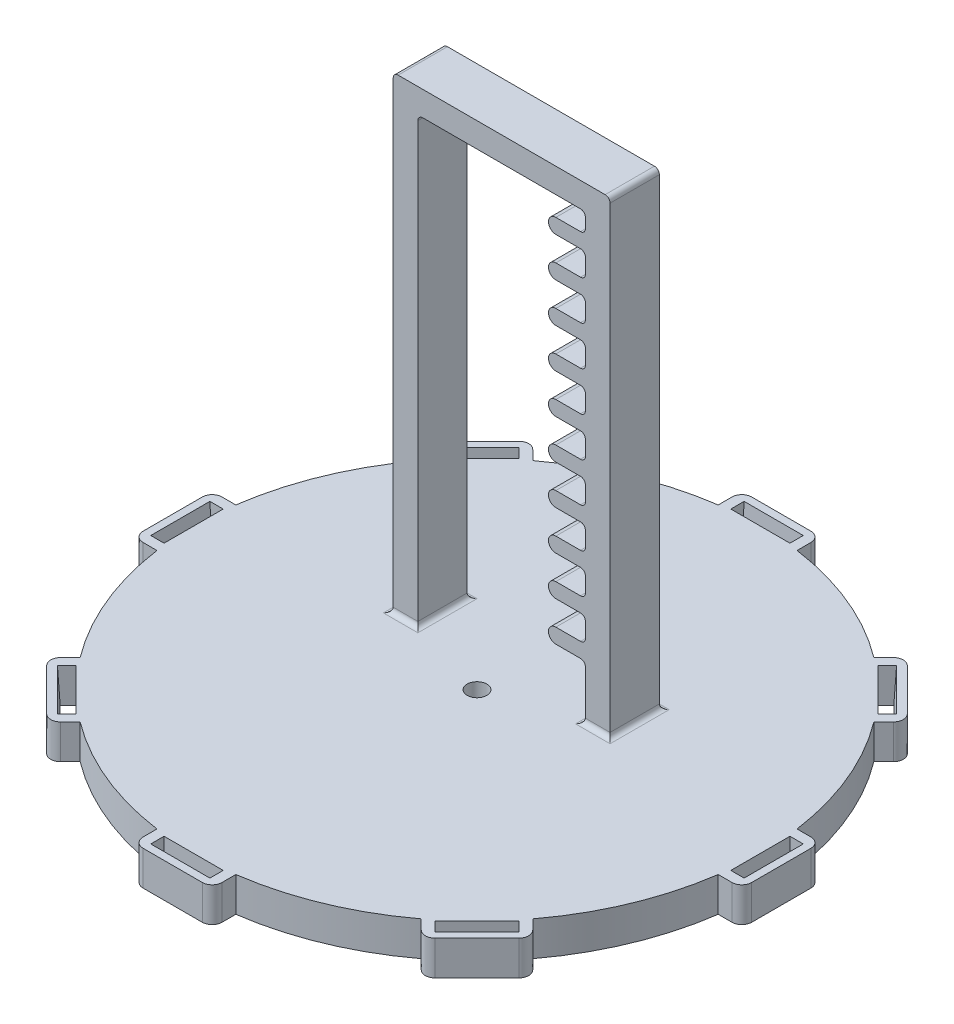
SolidWorks part; units mm, degrees
ref_plane "Front Plane" through (0, 0, 0) normal (0, 0, 1) x (1, 0, 0)
ref_plane "Top Plane" through (0, 0, 0) normal (0, 1, 0) x (1, 0, 0)
ref_plane "Right Plane" through (0, 0, 0) normal (1, 0, 0) x (0, 0, -1)
sketch "Sketch1" plane through (0, 0, 0) normal (0, 1, 0) x (1, 0, 0)
  line L0 (-8, 56.9408) -> (-8, 59.7408)
  line L1 (0, 57.5) -> (0, -57.5) construction
  line L2 (8, 56.9408) -> (8, 59.7408)
  line L3 (-6, 61.7408) -> (6, 61.7408)
  line L4 (39.4147, 47.8999) -> (47.8999, 39.4147)
  line L9 (34.6063, 45.9201) -> (36.5862, 47.8999)
  line L10 (45.9201, 34.6063) -> (47.8999, 36.5862)
  line L15 (61.7408, 6) -> (61.7408, -6)
  line L16 (56.9408, 8) -> (59.7408, 8)
  line L17 (56.9408, -8) -> (59.7408, -8)
  line L22 (47.8999, -39.4147) -> (39.4147, -47.8999)
  line L23 (45.9201, -34.6063) -> (47.8999, -36.5862)
  line L24 (34.6063, -45.9201) -> (36.5862, -47.8999)
  line L29 (6, -61.7408) -> (-6, -61.7408)
  line L30 (8, -56.9408) -> (8, -59.7408)
  line L31 (-8, -56.9408) -> (-8, -59.7408)
  line L36 (-39.4147, -47.8999) -> (-47.8999, -39.4147)
  line L37 (-34.6063, -45.9201) -> (-36.5862, -47.8999)
  line L38 (-45.9201, -34.6063) -> (-47.8999, -36.5862)
  line L43 (-61.7408, -6) -> (-61.7408, 6)
  line L44 (-56.9408, -8) -> (-59.7408, -8)
  line L45 (-56.9408, 8) -> (-59.7408, 8)
  line L50 (-47.8999, 39.4147) -> (-39.4147, 47.8999)
  line L51 (-45.9201, 34.6063) -> (-47.8999, 36.5862)
  line L52 (-34.6063, 45.9201) -> (-36.5862, 47.8999)
  arc A0 (-8, 56.9408) -> (-34.6063, 45.9201) centre (0, 0) ccw
  arc A1 (6, 61.7408) -> (8, 59.7408) centre (6, 59.7408) cw
  arc A2 (-6, 61.7408) -> (-8, 59.7408) centre (-6, 59.7408) ccw
  arc A3 (39.4147, 47.8999) -> (36.5862, 47.8999) centre (38.0005, 46.4857) ccw
  arc A4 (47.8999, 39.4147) -> (47.8999, 36.5862) centre (46.4857, 38.0005) cw
  arc A5 (61.7408, 6) -> (59.7408, 8) centre (59.7408, 6) ccw
  arc A6 (61.7408, -6) -> (59.7408, -8) centre (59.7408, -6) cw
  arc A7 (47.8999, -39.4147) -> (47.8999, -36.5862) centre (46.4857, -38.0005) ccw
  arc A8 (39.4147, -47.8999) -> (36.5862, -47.8999) centre (38.0005, -46.4857) cw
  arc A9 (6, -61.7408) -> (8, -59.7408) centre (6, -59.7408) ccw
  arc A10 (-6, -61.7408) -> (-8, -59.7408) centre (-6, -59.7408) cw
  arc A11 (-39.4147, -47.8999) -> (-36.5862, -47.8999) centre (-38.0005, -46.4857) ccw
  arc A12 (-47.8999, -39.4147) -> (-47.8999, -36.5862) centre (-46.4857, -38.0005) cw
  arc A13 (-61.7408, -6) -> (-59.7408, -8) centre (-59.7408, -6) ccw
  arc A14 (-61.7408, 6) -> (-59.7408, 8) centre (-59.7408, 6) cw
  arc A15 (-47.8999, 39.4147) -> (-47.8999, 36.5862) centre (-46.4857, 38.0005) ccw
  arc A16 (-39.4147, 47.8999) -> (-36.5862, 47.8999) centre (-38.0005, 46.4857) cw
  arc A17 (-45.9201, 34.6063) -> (-56.9408, 8) centre (0, 0) ccw
  arc A18 (-56.9408, -8) -> (-45.9201, -34.6063) centre (0, 0) ccw
  arc A19 (34.6063, 45.9201) -> (8, 56.9408) centre (0, 0) ccw
  arc A20 (-34.6063, -45.9201) -> (-8, -56.9408) centre (0, 0) ccw
  arc A21 (8, -56.9408) -> (34.6063, -45.9201) centre (0, 0) ccw
  arc A22 (45.9201, -34.6063) -> (56.9408, -8) centre (0, 0) ccw
  arc A23 (56.9408, 8) -> (45.9201, 34.6063) centre (0, 0) ccw
  point P11 (8, 61.7408)
  point P14 (-8, 61.7408)
  point P17 (-8, 58.3408)
  point P98 (0, 0)
  dimension "D1" = 115
  dimension "D2" = 2
  dimension "D3" = 16
  dimension "D4" = 2.8
  dimension "D7" = 8
extrude "Boss-Extrude1" add sketch "Sketch1" along normal blind 7
sketch "Sketch2" plane through (0, 7, 0) normal (0, 1, 0) x (1, 0, 0)
  line L0 (-57.5, 0) -> (57.5, 0) construction
  line L1 (0, 0) -> (0, 10) construction
  line L7 (17, 5) -> (22, 5)
  line L14 (0, 10) -> (29.7122, 10) construction
  line L15 (0, 10) -> (-19.5, 10) construction
  line L17 (17, 5) -> (17, 15)
  line L18 (-22, 15) -> (-17, 15)
  line L19 (-22, 15) -> (-22, 5)
  line L20 (-22, 5) -> (-17, 5)
  line L21 (-17, 15) -> (-17, 5)
  line L22 (-22, 15) -> (-17, 5) construction
  line L23 (-22, 5) -> (-17, 15) construction
  line L24 (17, 15) -> (22, 15)
  line L25 (22, 5) -> (22, 15)
  line L26 (17, 5) -> (22, 15) construction
  line L27 (17, 15) -> (22, 5) construction
  circle A0 centre (0, 0) radius 57.5 construction
  point P8 (19.5, 10)
  dimension "D1" = 10
  dimension "D2" = 17
  dimension "D3" = 17
  dimension "D4" = 10
  dimension "D5" = 5
  dimension "D6" = 10
  dimension "D7" = 5
extrude "Boss-Extrude2" add sketch "Sketch2" along normal blind 95
sketch "Sketch15" plane through (0, 0, 0) normal (0, -1, 0) x (1, 0, 0)
  circle A0 centre (0, 0) radius 2
  dimension "D1" = 4
extrude "Cut-Extrude3" cut sketch "Sketch15" along direction (0, 1, 0) on the side against the normal up to surface (7 mm away) contours A0 up to face at (0, 7, 0)
sketch "Sketch16" plane through (0, 0, 0) normal (0, -1, 0) x (1, 0, 0)
  line L1 (-6, 59.8) -> (6, 59.8)
  line L2 (-6, 59.8) -> (-6, 57.5)
  line L3 (-6, 57.5) -> (6, 57.5)
  line L4 (6, 59.8) -> (6, 57.5)
  point P5 (0, 57.5)
  dimension "D1" = 2.3
  dimension "D2" = 12
  dimension "D3" = 57.5
sketch "Sketch17" plane through (0, 7, 0) normal (0, 1, 0) x (1, 0, 0)
  line L0 (-6, -57.5) -> (6, -57.5) construction
  line L1 (-6, -57.5) -> (6, -57.5)
  line L2 (-6, -57.5) -> (-6, -60.2)
  line L3 (-6, -60.2) -> (6, -60.2)
  line L4 (6, -60.2) -> (6, -57.5)
  dimension "D1" = 2.7
ref_axis "Axis1" through (0, 107.1, 0) along (0, -1, 0)
loft "Cut-Loft2" cut profiles "Sketch16", "Sketch17" connector at (6, 0, 59.8) connector at (6, 7, 60.2)
pattern_circular "CirPattern1" count 8 over 360 about axis through (0, 107.1, 0) along (0, -1, 0) of "Cut-Loft2"
sketch "Sketch18" plane through (-17, 0, 0) normal (1, 0, 0) x (0, 0, -1)
  line L0 (15, 102) -> (15, 7) construction
  line L1 (5, 102) -> (15, 102)
  line L2 (5, 102) -> (5, 97)
  line L3 (5, 97) -> (15, 97)
  line L4 (15, 102) -> (15, 97)
  dimension "D1" = 5
extrude "Boss-Extrude3" add sketch "Sketch18" along normal up to surface (34 mm away) up to face at (17, 54.5, -10)
sketch "Sketch19" plane through (0, 0, -15) normal (0, 0, -1) x (-1, 0, 0)
  line L0 (-17, 93) -> (-11, 93)
  line L1 (-17, 97) -> (-17, 7) construction
  line L4 (-11, 91.5) -> (-19.8185, 91.5) construction
  line L5 (-17, 90) -> (-11, 90)
  line L6 (-17, 93) -> (-17, 90)
  arc A1 (-11, 93) -> (-11, 90) centre (-11, 91.5) cw
  dimension "D1" = 6
  dimension "D4" = 3
  dimension "D3" = 4
extrude "Boss-Extrude4" add sketch "Sketch19" against normal blind 10
fillet "Fillet1" radius 1 2 edges at (17, 93, -10) (17, 90, -10)
fillet "Fillet2" radius 1 12 edges at (-22, 102, -10) (22, 102, -10) (17, 7, -10) (19.5, 7, -15) (19.5, 7, -5) (22, 7, -10) (-19.5, 7, -5) (-19.5, 7, -15) (-22, 7, -10) (-17, 7, -10) (-17, 97, -10) (17, 97, -10)
pattern_linear "LPattern2" count 10 spacing 8 along (0, -1, 0) of "Fillet1", "Boss-Extrude4"
equation "\"85.00.00mm\"=8500"
